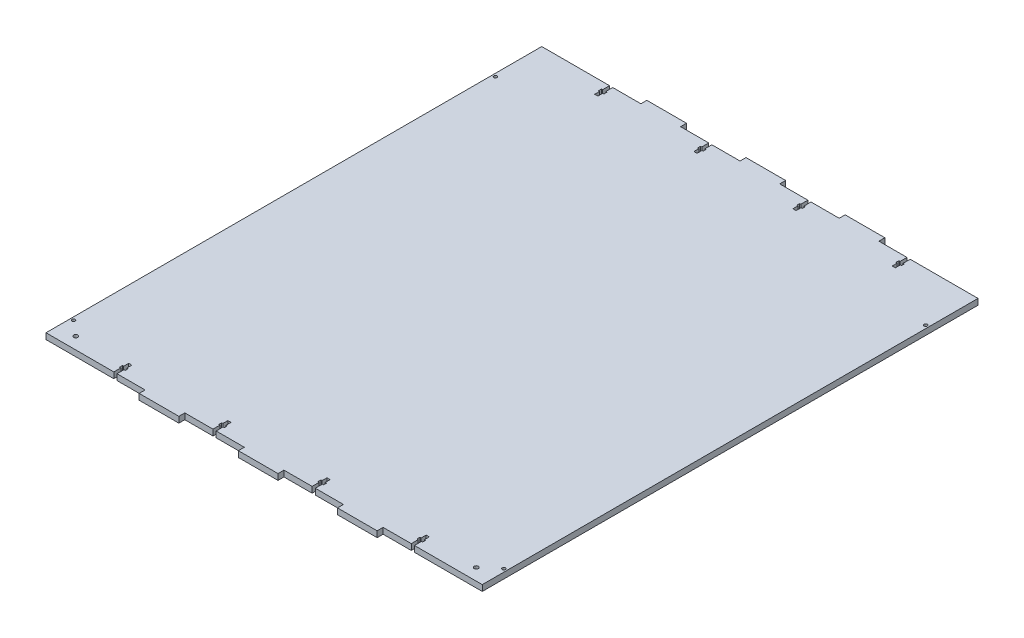
SolidWorks part; units mm, degrees
ref_plane "Front Plane" through (0, 0, 0) normal (0, 0, 1) x (1, 0, 0)
ref_plane "Top Plane" through (0, 0, 0) normal (0, 1, 0) x (1, 0, 0)
ref_plane "Right Plane" through (0, 0, 0) normal (1, 0, 0) x (0, 0, -1)
sketch "Sketch1" plane through (0, 0, 0) normal (0, 1, 0) x (1, 0, 0)
  line L1 (-220, -250) -> (220, -250)
  line L2 (-220, -250) -> (-220, 250)
  line L3 (-220, 250) -> (220, 250)
  line L4 (220, -250) -> (220, 250)
  line L5 (-220, -250) -> (220, 250) construction
  line L6 (-220, 250) -> (220, -250) construction
  point P0 (0, 0)
  dimension "D1" = 440
  dimension "D2" = 500
extrude "Boss-Extrude1" add sketch "Sketch1" along normal blind 6
sketch "Sketch2" plane through (0, 0, 0) normal (0, -1, 0) x (1, 0, 0)
  line L14 (0, 0) -> (0, 133.2527) construction
  line L15 (0, 0) -> (-145.1849, 0) construction
  line L40 (-148.4, 256) -> (-151.6, 256) construction
  line L41 (-148.4, 256) -> (-151.6, 256) construction
  line L42 (-48.4, 256) -> (-51.6, 256) construction
  line L43 (-48.4, 256) -> (-51.6, 256) construction
  line L44 (-148.4, 256) -> (-51.6, 256) construction
  line L45 (-220, 250) -> (220, 250) construction
  line L46 (-120, 256) -> (-80, 256)
  line L47 (-120, 256) -> (-120, 250)
  line L48 (-120, 250) -> (-80, 250)
  line L49 (-80, 256) -> (-80, 250)
  line L50 (-20, 250) -> (20, 250)
  line L51 (20, 256) -> (20, 250)
  line L52 (-20, 256) -> (20, 256)
  line L53 (-20, 256) -> (-20, 250)
  line L54 (80, 250) -> (120, 250)
  line L55 (120, 256) -> (120, 250)
  line L56 (80, 256) -> (120, 256)
  line L57 (80, 256) -> (80, 250)
  line L58 (120, -256) -> (120, -250)
  line L59 (80, -250) -> (120, -250)
  line L60 (80, -256) -> (120, -256)
  line L61 (80, -256) -> (80, -250)
  line L62 (20, -256) -> (20, -250)
  line L63 (-20, -256) -> (20, -256)
  line L64 (-20, -250) -> (20, -250)
  line L65 (-20, -256) -> (-20, -250)
  line L66 (-120, -250) -> (-80, -250)
  line L67 (-120, -256) -> (-120, -250)
  line L68 (-120, -256) -> (-80, -256)
  line L69 (-80, -256) -> (-80, -250)
  point P50 (-100, 256)
  dimension "D3" = 40
  dimension "D4" = 3
extrude "Boss-Extrude2" add sketch "Sketch2" against normal blind 6
sketch "Sketch3" plane through (0, 0, 0) normal (0, -1, 0) x (1, 0, 0)
  line L1 (214, 226.85) -> (220, 223.65) construction
  line L2 (214, -198.65) -> (220, -201.85) construction
  line L6 (214, 226.85) -> (214, 223.65)
  line L7 (214, 223.65) -> (220, 223.65)
  line L8 (220, 223.65) -> (220, 226.85)
  line L9 (220, 226.85) -> (214, 226.85)
  line L10 (214, 226.85) -> (214, 223.65) construction
  line L11 (214, 223.65) -> (220, 223.65) construction
  line L12 (220, 223.65) -> (220, 226.85) construction
  line L13 (220, 226.85) -> (214, 226.85) construction
  line L14 (214, -198.65) -> (214, -201.85)
  line L15 (214, -201.85) -> (220, -201.85)
  line L16 (220, -201.85) -> (220, -198.65)
  line L17 (220, -198.65) -> (214, -198.65)
  line L18 (214, -198.65) -> (214, -201.85) construction
  line L19 (214, -201.85) -> (220, -201.85) construction
  line L20 (220, -201.85) -> (220, -198.65) construction
  line L21 (220, -198.65) -> (214, -198.65) construction
  line L86 (0, 0) -> (0, 128.8409) construction
  line L166 (-151.6, -256) -> (-148.4, -256) construction
  line L167 (-151.6, -256) -> (-148.4, -256) construction
  line L168 (-150, -256) -> (-150, -234.6121) construction
  line L169 (-120, -250) -> (-220, -250) construction
  line L170 (-151.6, -235) -> (-148.4, -235)
  line L171 (-151.6, -235) -> (-151.6, -240)
  line L172 (-151.6, -250) -> (-148.4, -250)
  line L173 (-148.4, -235) -> (-148.4, -240)
  line L174 (-151.6, -235) -> (-148.4, -250) construction
  line L175 (-151.6, -250) -> (-148.4, -235) construction
  line L176 (-148.4, -243) -> (-147.2, -243)
  line L177 (-152.8, -243) -> (-151.6, -243)
  line L178 (-152.8, -243) -> (-152.8, -240)
  line L179 (-152.8, -240) -> (-151.6, -240)
  line L180 (-147.2, -243) -> (-147.2, -240)
  line L181 (-152.8, -243) -> (-147.2, -240) construction
  line L182 (-152.8, -240) -> (-147.2, -243) construction
  line L183 (-151.6, -243) -> (-151.6, -250)
  line L184 (-148.4, -243) -> (-148.4, -250)
  line L185 (-148.4, -240) -> (-147.2, -240)
  line L186 (-51.6, -235) -> (-48.4, -235)
  line L187 (-51.6, -235) -> (-51.6, -240)
  line L188 (-51.6, -250) -> (-48.4, -250)
  line L189 (-48.4, -235) -> (-48.4, -240)
  line L190 (-48.4, -243) -> (-47.2, -243)
  line L191 (-52.8, -243) -> (-51.6, -243)
  line L192 (-52.8, -243) -> (-52.8, -240)
  line L193 (-52.8, -240) -> (-51.6, -240)
  line L194 (-47.2, -243) -> (-47.2, -240)
  line L195 (-51.6, -243) -> (-51.6, -250)
  line L196 (-48.4, -243) -> (-48.4, -250)
  line L197 (-48.4, -240) -> (-47.2, -240)
  line L198 (-51.6, -235) -> (-48.4, -250) construction
  line L199 (-51.6, -250) -> (-48.4, -235) construction
  line L200 (-52.8, -243) -> (-47.2, -240) construction
  line L201 (-52.8, -240) -> (-47.2, -243) construction
  line L202 (48.4, -235) -> (51.6, -235)
  line L203 (48.4, -235) -> (48.4, -240)
  line L204 (48.4, -250) -> (51.6, -250)
  line L205 (51.6, -235) -> (51.6, -240)
  line L206 (51.6, -243) -> (52.8, -243)
  line L207 (47.2, -243) -> (48.4, -243)
  line L208 (47.2, -243) -> (47.2, -240)
  line L209 (47.2, -240) -> (48.4, -240)
  line L210 (52.8, -243) -> (52.8, -240)
  line L211 (48.4, -243) -> (48.4, -250)
  line L212 (51.6, -243) -> (51.6, -250)
  line L213 (51.6, -240) -> (52.8, -240)
  line L214 (48.4, -235) -> (51.6, -250) construction
  line L215 (48.4, -250) -> (51.6, -235) construction
  line L216 (47.2, -243) -> (52.8, -240) construction
  line L217 (47.2, -240) -> (52.8, -243) construction
  line L218 (148.4, -235) -> (151.6, -235)
  line L219 (148.4, -235) -> (148.4, -240)
  line L220 (148.4, -250) -> (151.6, -250)
  line L221 (151.6, -235) -> (151.6, -240)
  line L222 (151.6, -243) -> (152.8, -243)
  line L223 (147.2, -243) -> (148.4, -243)
  line L224 (147.2, -243) -> (147.2, -240)
  line L225 (147.2, -240) -> (148.4, -240)
  line L226 (152.8, -243) -> (152.8, -240)
  line L227 (148.4, -243) -> (148.4, -250)
  line L228 (151.6, -243) -> (151.6, -250)
  line L229 (151.6, -240) -> (152.8, -240)
  line L230 (148.4, -235) -> (151.6, -250) construction
  line L231 (148.4, -250) -> (151.6, -235) construction
  line L232 (147.2, -243) -> (152.8, -240) construction
  line L233 (147.2, -240) -> (152.8, -243) construction
  line L235 (147.2, 240) -> (152.8, 243) construction
  line L236 (147.2, 243) -> (152.8, 240) construction
  line L237 (148.4, 250) -> (151.6, 235) construction
  line L238 (148.4, 235) -> (151.6, 250) construction
  line L239 (47.2, 240) -> (52.8, 243) construction
  line L240 (47.2, 243) -> (52.8, 240) construction
  line L241 (48.4, 250) -> (51.6, 235) construction
  line L242 (48.4, 235) -> (51.6, 250) construction
  line L243 (-52.8, 240) -> (-47.2, 243) construction
  line L244 (-52.8, 243) -> (-47.2, 240) construction
  line L245 (-51.6, 250) -> (-48.4, 235) construction
  line L246 (-51.6, 235) -> (-48.4, 250) construction
  line L247 (-152.8, 240) -> (-147.2, 243) construction
  line L248 (-152.8, 243) -> (-147.2, 240) construction
  line L249 (-151.6, 250) -> (-148.4, 235) construction
  line L250 (-151.6, 235) -> (-148.4, 250) construction
  line L251 (151.6, 240) -> (152.8, 240)
  line L252 (151.6, 243) -> (151.6, 250)
  line L253 (148.4, 243) -> (148.4, 250)
  line L254 (152.8, 243) -> (152.8, 240)
  line L255 (147.2, 240) -> (148.4, 240)
  line L256 (147.2, 243) -> (147.2, 240)
  line L257 (147.2, 243) -> (148.4, 243)
  line L258 (151.6, 243) -> (152.8, 243)
  line L259 (151.6, 235) -> (151.6, 240)
  line L260 (148.4, 250) -> (151.6, 250)
  line L261 (148.4, 235) -> (148.4, 240)
  line L262 (148.4, 235) -> (151.6, 235)
  line L263 (51.6, 240) -> (52.8, 240)
  line L264 (51.6, 243) -> (51.6, 250)
  line L265 (48.4, 243) -> (48.4, 250)
  line L266 (52.8, 243) -> (52.8, 240)
  line L267 (47.2, 240) -> (48.4, 240)
  line L268 (47.2, 243) -> (47.2, 240)
  line L269 (47.2, 243) -> (48.4, 243)
  line L270 (51.6, 243) -> (52.8, 243)
  line L271 (51.6, 235) -> (51.6, 240)
  line L272 (48.4, 250) -> (51.6, 250)
  line L273 (48.4, 235) -> (48.4, 240)
  line L274 (48.4, 235) -> (51.6, 235)
  line L275 (-48.4, 240) -> (-47.2, 240)
  line L276 (-48.4, 243) -> (-48.4, 250)
  line L277 (-51.6, 243) -> (-51.6, 250)
  line L278 (-47.2, 243) -> (-47.2, 240)
  line L279 (-52.8, 240) -> (-51.6, 240)
  line L280 (-52.8, 243) -> (-52.8, 240)
  line L281 (-52.8, 243) -> (-51.6, 243)
  line L282 (-48.4, 243) -> (-47.2, 243)
  line L283 (-48.4, 235) -> (-48.4, 240)
  line L284 (-51.6, 250) -> (-48.4, 250)
  line L285 (-51.6, 235) -> (-51.6, 240)
  line L286 (-51.6, 235) -> (-48.4, 235)
  line L287 (-148.4, 240) -> (-147.2, 240)
  line L288 (-148.4, 243) -> (-148.4, 250)
  line L289 (-151.6, 243) -> (-151.6, 250)
  line L290 (-147.2, 243) -> (-147.2, 240)
  line L291 (-152.8, 240) -> (-151.6, 240)
  line L292 (-152.8, 243) -> (-152.8, 240)
  line L293 (-152.8, 243) -> (-151.6, 243)
  line L294 (-148.4, 243) -> (-147.2, 243)
  line L295 (-148.4, 235) -> (-148.4, 240)
  line L296 (-151.6, 250) -> (-148.4, 250)
  line L297 (-151.6, 235) -> (-151.6, 240)
  line L298 (-151.6, 235) -> (-148.4, 235)
  circle A0 centre (217, 225.25) radius 1.6
  circle A1 centre (217, -200.25) radius 1.6
  circle A2 centre (-217, -200.25) radius 1.6
  circle A3 centre (-217, 225.25) radius 1.6
  circle A4 centre (202, 238) radius 2.1 construction
  circle A5 centre (202, 238) radius 2.1
  circle A6 centre (-202, 238) radius 2.1 construction
  circle A7 centre (-202, 238) radius 2.1
  point P154 (-150, -242.5)
  point P161 (-150, -241.5)
  point P171 (-50, -242.5)
  point P176 (-50, -241.5)
  point P185 (50, -242.5)
  point P190 (50, -241.5)
  point P199 (150, -242.5)
  point P204 (150, -241.5)
  point P261 (150, 241.5)
  point P262 (150, 242.5)
  point P263 (50, 241.5)
  point P264 (50, 242.5)
  point P265 (-50, 241.5)
  point P266 (-50, 242.5)
  point P267 (-150, 241.5)
  point P268 (-150, 242.5)
  line M6 (220, 250) -> (120, 250)
  line M10 (80, 250) -> (20, 250)
  line M14 (-20, 250) -> (-80, 250)
  line M18 (-120, 250) -> (-220, 250)
  line M20 (-220, -250) -> (-120, -250)
  line M24 (-80, -250) -> (-20, -250)
  line M28 (20, -250) -> (80, -250)
  line M32 (120, -250) -> (220, -250)
  dimension "D1" = 0
  dimension "D2" = 0
  dimension "D6" = 15
  dimension "D7" = 5.6
  dimension "D8" = 7
  dimension "D9" = 4
extrude "Cut-Extrude1" cut sketch "Sketch3" against normal through all contours L185 L173 L170 L171 L179 L178 L177 L183 L184 L176 L180 M20 | L197 L189 L186 L187 L193 L192 L191 L195 L196 L190 L194 M24 | L213 L205 L202 L203 L209 L208 L207 L211 L212 L206 L210 M28 | L229 L221 L218 L219 L225 L224 L223 L227 L228 L222 L226 M32 | L297 L298 L295 L287 L290 L294 L288 L289 L293 L292 L291 M18 | L285 L286 L283 L275 L278 L282 L276 L277 L281 L280 L279 M14 | L273 L274 L271 L263 L266 L270 L264 L265 L269 L268 L267 M10 | L261 L262 L259 L251 L254 L258 L252 L253 L257 L256 L255 M6 | A1 | A0 | A3 | A2 | A7 | A5
